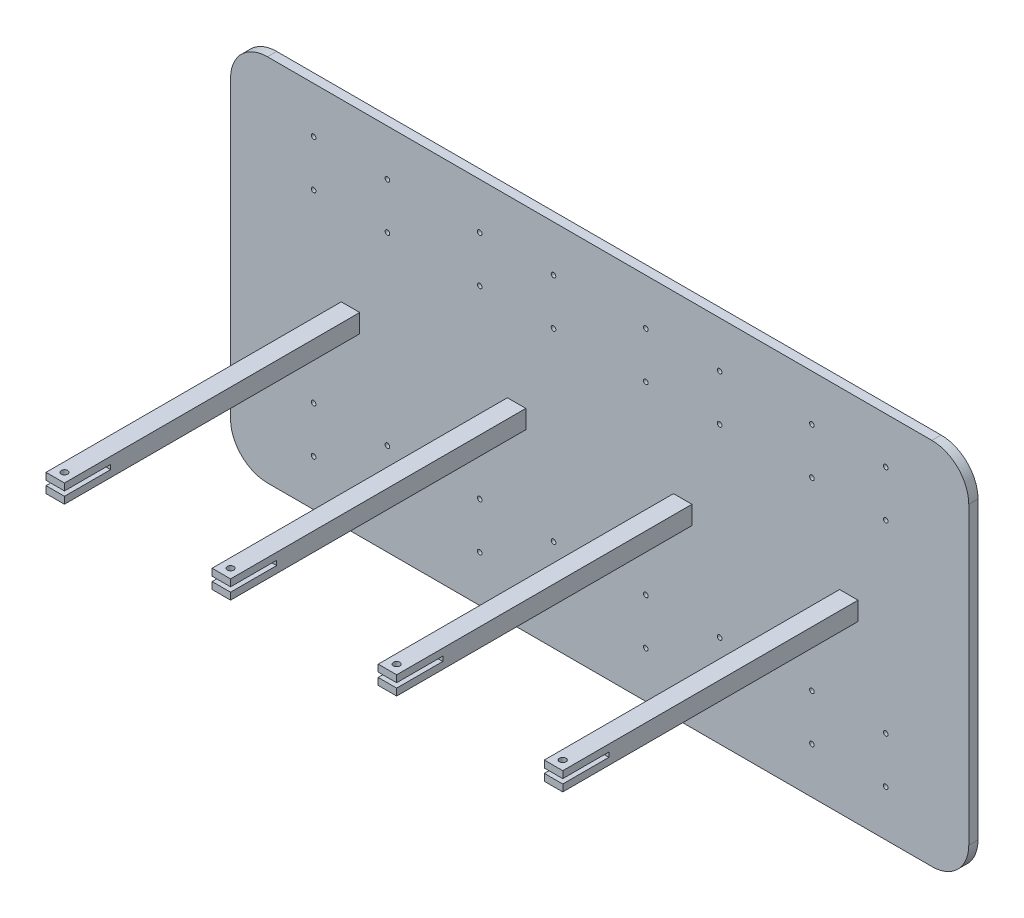
SolidWorks part; units mm, degrees
ref_plane "Front Plane" through (0, 0, 0) normal (0, 0, 1) x (1, 0, 0)
ref_plane "Top Plane" through (0, 0, 0) normal (0, 1, 0) x (1, 0, 0)
ref_plane "Right Plane" through (0, 0, 0) normal (1, 0, 0) x (0, 0, -1)
sketch "Sketch1" plane through (0, 0, 0) normal (0, 0, 1) x (1, 0, 0)
  line L0 (0, 200) -> (0, -200) construction
  line L1 (-360, 200) -> (360, 200)
  line L2 (-400, 160) -> (-400, -160)
  line L3 (-360, -200) -> (360, -200)
  line L4 (400, 160) -> (400, -160)
  line L5 (-180, 200) -> (-180, -200) construction
  line L6 (180, 200) -> (180, -200) construction
  line L7 (400, 0) -> (-400, 0) construction
  line L8 (360, 200) -> (360, -200) construction
  line L11 (-360, 200) -> (-360, -200) construction
  line L14 (140, 152.5) -> (140, 97.5)
  line L15 (310, 162.5) -> (230, 162.5)
  line L16 (320, 152.5) -> (320, 97.5)
  line L17 (310, 87.5) -> (230, 87.5)
  line L23 (220, 152.5) -> (220, 97.5)
  line L24 (50, 87.5) -> (130, 87.5)
  line L25 (40, 152.5) -> (40, 97.5)
  line L26 (50, 162.5) -> (130, 162.5)
  line L27 (-310, -162.5) -> (-230, -162.5)
  line L28 (-320, -152.5) -> (-320, -97.5)
  line L32 (-310, -87.5) -> (-230, -87.5)
  line L33 (-220, -152.5) -> (-220, -97.5)
  line L34 (-50, 162.5) -> (-130, 162.5)
  line L35 (-40, 152.5) -> (-40, 97.5)
  line L36 (-50, 87.5) -> (-130, 87.5)
  line L37 (-140, 152.5) -> (-140, 97.5)
  line L38 (-220, 152.5) -> (-220, 97.5)
  line L39 (-310, 87.5) -> (-230, 87.5)
  line L40 (-320, 152.5) -> (-320, 97.5)
  line L41 (-310, 162.5) -> (-230, 162.5)
  line L42 (-140, -152.5) -> (-140, -97.5)
  line L43 (-50, -87.5) -> (-130, -87.5)
  line L44 (-40, -152.5) -> (-40, -97.5)
  line L45 (-50, -162.5) -> (-130, -162.5)
  line L46 (50, -162.5) -> (130, -162.5)
  line L47 (40, -152.5) -> (40, -97.5)
  line L48 (50, -87.5) -> (130, -87.5)
  line L49 (220, -152.5) -> (220, -97.5)
  line L50 (310, -87.5) -> (230, -87.5)
  line L51 (320, -152.5) -> (320, -97.5)
  line L52 (310, -162.5) -> (230, -162.5)
  line L53 (140, -152.5) -> (140, -97.5)
  line L54 (-270, 200) -> (-270, -200) construction
  line L55 (-90, 200) -> (-90, -200) construction
  line L56 (90, 200) -> (90, -200) construction
  line L57 (270, 200) -> (270, -200) construction
  line L59 (260, -10) -> (280, -10)
  line L60 (260, -10) -> (260, 10)
  line L61 (260, 10) -> (280, 10)
  line L62 (280, -10) -> (280, 10)
  line L63 (260, -10) -> (280, 10) construction
  line L64 (260, 10) -> (280, -10) construction
  line L65 (80, -10) -> (100, -10)
  line L66 (80, -10) -> (80, 10)
  line L67 (80, 10) -> (100, 10)
  line L68 (100, -10) -> (100, 10)
  line L69 (80, -10) -> (100, 10) construction
  line L70 (80, 10) -> (100, -10) construction
  line L71 (-100, -10) -> (-80, -10)
  line L72 (-100, -10) -> (-100, 10)
  line L73 (-100, 10) -> (-80, 10)
  line L74 (-80, -10) -> (-80, 10)
  line L75 (-100, -10) -> (-80, 10) construction
  line L76 (-100, 10) -> (-80, -10) construction
  line L77 (-280, -10) -> (-260, -10)
  line L78 (-280, -10) -> (-280, 10)
  line L79 (-280, 10) -> (-260, 10)
  line L80 (-260, -10) -> (-260, 10)
  line L81 (-280, -10) -> (-260, 10) construction
  line L82 (-280, 10) -> (-260, -10) construction
  arc A0 (360, 200) -> (400, 160) centre (360, 160) cw
  arc A1 (360, -200) -> (400, -160) centre (360, -160) ccw
  arc A2 (-360, -200) -> (-400, -160) centre (-360, -160) cw
  arc A3 (-360, 200) -> (-400, 160) centre (-360, 160) ccw
  arc A4 (230, 87.5) -> (220, 97.5) centre (230, 97.5) cw
  arc A5 (310, 87.5) -> (320, 97.5) centre (310, 97.5) ccw
  arc A6 (310, 162.5) -> (320, 152.5) centre (310, 152.5) cw
  arc A7 (220, 152.5) -> (230, 162.5) centre (230, 152.5) cw
  circle A8 centre (310, 150) radius 2.5
  circle A9 centre (230, 150) radius 2.5
  circle A10 centre (230, 100) radius 2.5
  circle A11 centre (310, 100) radius 2.5
  circle A12 centre (50, 100) radius 2.5
  circle A13 centre (130, 100) radius 2.5
  circle A14 centre (130, 150) radius 2.5
  circle A15 centre (50, 150) radius 2.5
  arc A23 (140, 152.5) -> (130, 162.5) centre (130, 152.5) ccw
  arc A27 (50, 162.5) -> (40, 152.5) centre (50, 152.5) ccw
  arc A36 (50, 87.5) -> (40, 97.5) centre (50, 97.5) cw
  arc A40 (130, 87.5) -> (140, 97.5) centre (130, 97.5) ccw
  arc A41 (-230, -87.5) -> (-220, -97.5) centre (-230, -97.5) cw
  arc A42 (-310, -87.5) -> (-320, -97.5) centre (-310, -97.5) ccw
  arc A43 (-310, -162.5) -> (-320, -152.5) centre (-310, -152.5) cw
  arc A44 (-220, -152.5) -> (-230, -162.5) centre (-230, -152.5) cw
  circle A45 centre (-310, -150) radius 2.5
  circle A46 centre (-230, -150) radius 2.5
  circle A47 centre (-230, -100) radius 2.5
  circle A48 centre (-310, -100) radius 2.5
  arc A49 (-130, 87.5) -> (-140, 97.5) centre (-130, 97.5) cw
  arc A50 (-50, 87.5) -> (-40, 97.5) centre (-50, 97.5) ccw
  arc A51 (-50, 162.5) -> (-40, 152.5) centre (-50, 152.5) cw
  arc A52 (-140, 152.5) -> (-130, 162.5) centre (-130, 152.5) cw
  circle A53 centre (-50, 150) radius 2.5
  circle A54 centre (-130, 150) radius 2.5
  circle A55 centre (-130, 100) radius 2.5
  circle A56 centre (-50, 100) radius 2.5
  circle A57 centre (-310, 100) radius 2.5
  circle A58 centre (-230, 100) radius 2.5
  circle A59 centre (-230, 150) radius 2.5
  circle A60 centre (-310, 150) radius 2.5
  arc A61 (-220, 152.5) -> (-230, 162.5) centre (-230, 152.5) ccw
  arc A62 (-310, 162.5) -> (-320, 152.5) centre (-310, 152.5) ccw
  arc A63 (-310, 87.5) -> (-320, 97.5) centre (-310, 97.5) cw
  arc A64 (-230, 87.5) -> (-220, 97.5) centre (-230, 97.5) ccw
  circle A65 centre (-50, -100) radius 2.5
  circle A66 centre (-130, -100) radius 2.5
  circle A67 centre (-130, -150) radius 2.5
  circle A68 centre (-50, -150) radius 2.5
  arc A69 (-140, -152.5) -> (-130, -162.5) centre (-130, -152.5) ccw
  arc A70 (-50, -162.5) -> (-40, -152.5) centre (-50, -152.5) ccw
  arc A71 (-50, -87.5) -> (-40, -97.5) centre (-50, -97.5) cw
  arc A72 (-130, -87.5) -> (-140, -97.5) centre (-130, -97.5) ccw
  arc A73 (130, -87.5) -> (140, -97.5) centre (130, -97.5) cw
  arc A74 (50, -87.5) -> (40, -97.5) centre (50, -97.5) ccw
  arc A75 (50, -162.5) -> (40, -152.5) centre (50, -152.5) cw
  arc A76 (140, -152.5) -> (130, -162.5) centre (130, -152.5) cw
  circle A77 centre (50, -150) radius 2.5
  circle A78 centre (130, -150) radius 2.5
  circle A79 centre (130, -100) radius 2.5
  circle A80 centre (50, -100) radius 2.5
  circle A81 centre (310, -100) radius 2.5
  circle A82 centre (230, -100) radius 2.5
  circle A83 centre (230, -150) radius 2.5
  circle A84 centre (310, -150) radius 2.5
  arc A85 (220, -152.5) -> (230, -162.5) centre (230, -152.5) ccw
  arc A86 (310, -162.5) -> (320, -152.5) centre (310, -152.5) ccw
  arc A87 (310, -87.5) -> (320, -97.5) centre (310, -97.5) cw
  arc A88 (230, -87.5) -> (220, -97.5) centre (230, -97.5) ccw
  point P4 (-400, 0)
  point P6 (400, 0)
  point P7 (0, 200)
  point P8 (0, -200)
  point P11 (400, 200)
  point P14 (400, -200)
  point P19 (-400, 200)
  point P28 (0, 0)
  point P36 (320, 87.5)
  point P39 (320, 162.5)
  point P42 (220, 162.5)
  point P44 (270, 162.5)
  point P46 (220, 125)
  point P78 (140, 162.5)
  point P79 (40, 162.5)
  point P80 (40, 87.5)
  point P124 (-40, 87.5)
  point P125 (-40, 162.5)
  point P126 (-140, 162.5)
  point P147 (-220, 162.5)
  point P148 (-320, 162.5)
  point P149 (-320, 87.5)
  point P207 (-320, -87.5)
  point P208 (-320, -162.5)
  point P209 (-220, -162.5)
  point P210 (-140, -162.5)
  point P211 (-40, -162.5)
  point P212 (-40, -87.5)
  point P213 (40, -87.5)
  point P214 (40, -162.5)
  point P215 (140, -162.5)
  point P216 (220, -162.5)
  point P217 (320, -162.5)
  point P218 (320, -87.5)
  point P223 (270, 0)
  point P228 (90, 0)
  point P233 (-90, 0)
  point P238 (-270, 0)
  point P243 (0, 0)
  dimension "D3" = 40
  dimension "D9" = 90
  dimension "D10" = 125
  dimension "D11" = 5
  dimension "D19" = 90
  dimension "D12" = 10
  dimension "D13" = 10
  dimension "D14" = 12.5
  dimension "D15" = 12.5
  dimension "D16" = 90
  dimension "D8" = 10
  dimension "D1" = 800
  dimension "D2" = 400
  dimension "D4" = 180
  dimension "D5" = 180
  dimension "D6" = 100
  dimension "D7" = 75
  dimension "D17" = 20
  dimension "D18" = 90
  dimension "D20" = 90
  dimension "D21" = 90
extrude "Boss-Extrude8" add sketch "Sketch1" against normal blind 10 contours A76 L53 A73 L48 A74 L47 A75 L46 A80 A79 A78 A77 | L43 A72 L42 A69 L45 A70 L44 A71 A68 A66 A65 A67 | L50 A88 L49 A85 L52 A86 L51 A87 A84 A82 A81 A83 | A7 L23 A4 L17 A5 L16 A6 L15 A11 A10 A9 A8 | L24 A40 L14 A23 L26 A27 L25 A36 A15 A13 A12 A14 | A52 L37 A49 L36 A50 L35 A51 L34 A56 A55 A54 A53 | L39 A64 L38 A61 L41 A62 L40 A63 A60 A58 A57 A59 | A44 L33 A41 L32 A42 L28 A43 L27 A48 A47 A46 A45 | L1 A3 L2 A2 L3 A1 L4 A0 A88 L50 A87 L51 A86 L52 A85 L49 A72 L43 A71 L44 A70 L45 A69 L42 A64 L39 A63 L40 A62 L41 A61 L38 A40 L24 A36 L25 A27 L26 A23 L14 L23 A7 L15 A6 L16 A5 region at (0, 0, 0) region at (90, 125, 0) region at (270, 125, 0) region at (-270, -125, 0) region at (-90, 125, 0) region at (-270, 125, 0) region at (-90, -125, 0) region at (90, -125, 0) region at (270, -125, 0)
extrude "Boss-Extrude9" add sketch "Sketch1<12>" along normal blind 320 contours L77 L80 L79 L78 | L71 L74 L73 L72 | L65 L68 L67 L66 | L59 L62 L61 L60 region at (270, 0, 0) region at (90, 0, 0) region at (-90, 0, 0) region at (-270, 0, 0)
sketch "Sketch1<12>" plane through (0, 0, 0) normal (0, 0, 1) x (1, 0, 0) same geometry as "Sketch1"
sketch "Sketch4" plane through (0, -10, 0) normal (0, -1, 0) x (1, 0, 0)
  line L0 (-280, 320) -> (-260, 320) construction
  line L5 (-280, 320) -> (-280, 0) construction
  line L6 (-100, 320) -> (-80, 320) construction
  line L8 (-100, 320) -> (-100, 0) construction
  line L9 (80, 320) -> (80, 0) construction
  line L10 (80, 320) -> (100, 320) construction
  line L11 (260, 320) -> (260, 0) construction
  line L12 (260, 320) -> (280, 320) construction
  circle A0 centre (-270, 310) radius 3.5
  circle A1 centre (-90, 310) radius 3.5
  circle A2 centre (90, 310) radius 3.5
  circle A3 centre (270, 310) radius 3.5
  point P4 (-270, 320)
  point P24 (90, 320)
  dimension "D1" = 7
  dimension "D4" = 10
  dimension "D2" = 10
  dimension "D3" = 10
  dimension "D5" = 10
  dimension "D6" = 10
  dimension "D7" = 10
  dimension "D8" = 10
  dimension "D9" = 10
extrude "Cut-Extrude14" cut sketch "Sketch4" against normal blind 210 contours A3 | A2 | A1 | A0
sketch "Sketch5" plane through (280, 0, 0) normal (1, 0, 0) x (0, 0, -1)
  line L1 (-320, -10) -> (-320, 10) construction
  line L2 (-320, 2.5) -> (-270, 2.5)
  line L3 (-320, 2.5) -> (-320, -2.5)
  line L4 (-320, -2.5) -> (-270, -2.5)
  line L6 (-270, 2.5) -> (-270, -2.5)
  point P6 (-270, 0)
  dimension "D1" = 50
  dimension "D2" = 5
extrude "Cut-Extrude18" cut sketch "Sketch5" against normal through all
